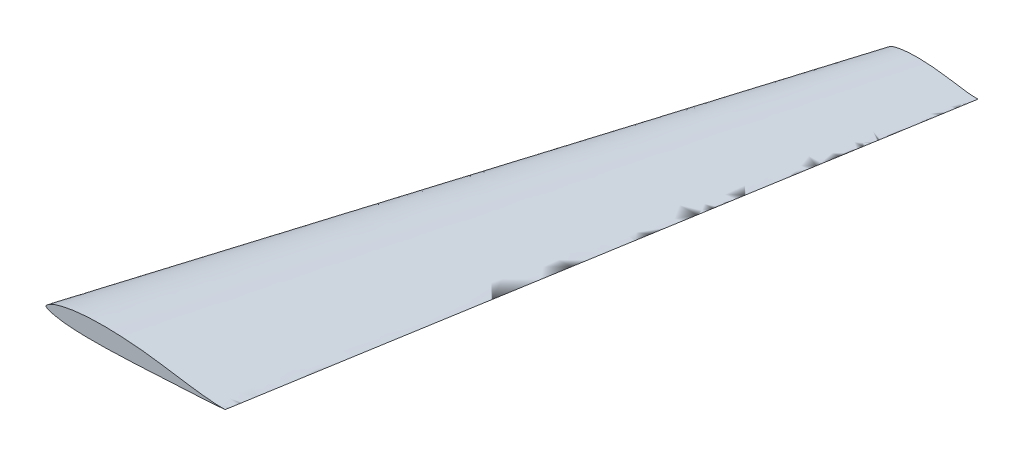
SolidWorks part; units mm, degrees
ref_plane "Front Plane" through (0, 0, 0) normal (0, 0, 1) x (1, 0, 0)
ref_plane "Top Plane" through (0, 0, 0) normal (0, 1, 0) x (1, 0, 0)
ref_plane "Right Plane" through (0, 0, 0) normal (1, 0, 0) x (0, 0, -1)
curve "Curve1"
  spline degree 3 poles (89.4117, -0.0768, 0) (90.1581, 0.0163, 0) (89.3384, -0.0489, 0) (88.6634, -0.0554, 0) (86.9988, -0.0528, 0) (84.9698, 0.0523, 0) (82.3441, 0.2429, 0) (79.2951, 0.5513, 0) (75.8494, 0.9741, 0) (72.0904, 1.4967, 0) (68.0818, 2.0963, 0) (63.8898, 2.7454, 0) (59.5721, 3.4086, 0) (55.1731, 4.0377, 0) (50.7294, 4.6, 0) (46.2733, 5.0781, 0) (41.8379, 5.4578, 0) (37.4583, 5.7341, 0) (33.171, 5.903, 0) (29.014, 5.9637, 0) (25.0243, 5.916, 0) (21.2371, 5.7575, 0) (17.6835, 5.491, 0) (14.3911, 5.12, 0) (11.385, 4.6544, 0) (8.6886, 4.1134, 0) (6.3249, 3.5134, 0) (4.3152, 2.87, 0) (2.6751, 2.2019, 0) (1.4179, 1.5316, 0) (0.6259, 0.9504, 0) (0.2409, 0.5277, 0) (0.0946, 0.3023, 0) (0.0289, 0.1579, 0) (-0.0008, 0.0428, 0) (-0.0021, -0.0493, 0) (0.0369, -0.1348, 0) (0.1141, -0.2351, 0) (0.2404, -0.3544, 0) (0.4668, -0.5223, 0) (1.0037, -0.8427, 0) (2.0204, -1.2501, 0) (3.5765, -1.7042, 0) (5.5485, -2.1302, 0) (7.9154, -2.5093, 0) (10.6594, -2.8252, 0) (13.7595, -3.0666, 0) (17.1926, -3.2314, 0) (20.9311, -3.3172, 0) (24.9437, -3.3283, 0) (29.1943, -3.2696, 0) (33.6423, -3.153, 0) (38.2418, -2.9882, 0) (42.9422, -2.7897, 0) (47.6888, -2.5669, 0) (52.4251, -2.3307, 0) (57.0933, -2.0873, 0) (61.6364, -1.844, 0) (65.999, -1.6043, 0) (70.1278, -1.373, 0) (73.9729, -1.1522, 0) (77.4858, -0.9472, 0) (80.6263, -0.7576, 0) (83.3439, -0.5873, 0) (85.6375, -0.4302, 0) (87.3906, -0.2992, 0) (88.8126, -0.1608, 0) (89.4117, -0.0768, 0) (90.1581, 0.0163, 0) (89.3384, -0.0489, 0) knots -0.013312 -0.00609 -0.00158 0 0.001669 0.006747 0.015187 0.026742 0.041155 0.058129 0.077283 0.098227 0.12058 0.143966 0.168018 0.192451 0.217075 0.24171 0.266182 0.29031 0.313903 0.336767 0.358704 0.37954 0.399122 0.417322 0.434037 0.449154 0.462553 0.474139 0.483848 0.491647 0.497539 0.499898 0.501005 0.501951 0.502492 0.502956 0.503431 0.504004 0.505035 0.506276 0.508636 0.515301 0.524213 0.535296 0.548467 0.563638 0.580726 0.599619 0.62018 0.642246 0.665633 0.690118 0.715452 0.741354 0.76752 0.793634 0.819375 0.844429 0.868488 0.891259 0.912467 0.93185 0.949165 0.964196 0.976755 0.986688 0.99391 0.99842 1 1.001669 1.006747 1.015187 periodic
sketch "CentralProfile" plane through (0, 0, 0) normal (0, 0, 1) x (1, 0, 0)
  line L0 (90, 0) -> (-10, 0) construction
  spline S1 degree 3 poles (89.3464, -0.0856) (90.1757, 0.0182) (89.2649, -0.0546) (88.5149, -0.0621) (86.6653, -0.0599) (84.4108, 0.0561) (81.4932, 0.2668) (78.1052, 0.6082) (74.2764, 1.0766) (70.0995, 1.6557) (65.6451, 2.3204) (60.9871, 3.0399) (56.1892, 3.7751) (51.3011, 4.4723) (46.3633, 5.0953) (41.4118, 5.6247) (36.4833, 6.0448) (31.6169, 6.35) (26.8531, 6.5359) (22.2341, 6.6017) (17.8011, 6.547) (13.593, 6.3694) (9.6446, 6.0718) (5.9865, 5.6583) (2.6465, 5.1398) (-0.3493, 4.5376) (-2.9754, 3.8699) (-5.2082, 3.1542) (-7.0304, 2.4112) (-8.4269, 1.6659) (-9.3068, 1.0198) (-9.7344, 0.5499) (-9.8969, 0.2994) (-9.9698, 0.1389) (-10.0028, 0.011) (-10.0042, -0.0913) (-9.9608, -0.1863) (-9.8749, -0.2977) (-9.7346, -0.4302) (-9.483, -0.6167) (-8.8862, -0.9725) (-7.7564, -1.4247) (-6.0272, -1.9287) (-3.8359, -2.4013) (-1.2058, -2.8215) (1.8433, -3.1713) (5.2881, -3.4383) (9.1027, -3.6201) (13.2568, -3.7139) (17.7152, -3.7245) (22.4382, -3.6576) (27.3805, -3.5263) (32.4911, -3.3413) (37.7137, -3.1189) (42.9878, -2.8693) (48.2503, -2.605) (53.4371, -2.3326) (58.4851, -2.0605) (63.3324, -1.7923) (67.92, -1.5337) (72.1923, -1.2867) (76.0955, -1.0576) (79.5849, -0.8456) (82.6045, -0.6553) (85.1528, -0.4797) (87.1007, -0.3335) (88.6807, -0.1791) (89.3464, -0.0856) (90.1757, 0.0182) (89.2649, -0.0546) knots -0.013312 -0.00609 -0.00158 0 0.001669 0.006747 0.015187 0.026742 0.041155 0.058129 0.077283 0.098227 0.12058 0.143966 0.168018 0.192451 0.217075 0.24171 0.266182 0.29031 0.313903 0.336767 0.358704 0.37954 0.399122 0.417322 0.434037 0.449154 0.462553 0.474139 0.483848 0.491647 0.497539 0.499898 0.501005 0.501951 0.502492 0.502956 0.503431 0.504004 0.505035 0.506276 0.508636 0.515301 0.524213 0.535296 0.548467 0.563638 0.580726 0.599619 0.62018 0.642246 0.665633 0.690118 0.715452 0.741354 0.76752 0.793634 0.819375 0.844429 0.868488 0.891259 0.912467 0.93185 0.949165 0.964196 0.976755 0.986688 0.99391 0.99842 1 1.001669 1.006747 1.015187 only from (90, 0) to (90, 0)
  point P1 (1.8051, -3.1475)
  point P2 (90, 0)
  point P4 (1.8148, 4.9626)
  dimension "D1" = 100
ref_plane "CentralProfilePlane" through (0, 0, 0) normal (0, 0, 1) x (1, 0, 0)
curve "Curve2"
  spline degree 3 poles (49.6732, -0.0427, -360) (50.0878, 0.0091, -360) (49.6325, -0.0272, -360) (49.2574, -0.0308, -360) (48.3327, -0.0294, -360) (47.2055, 0.0291, -360) (45.7467, 0.1349, -360) (44.0528, 0.3063, -360) (42.1386, 0.5412, -360) (40.0502, 0.8315, -360) (37.8232, 1.1646, -360) (35.4944, 1.5252, -360) (33.0956, 1.8937, -360) (30.6517, 2.2432, -360) (28.183, 2.5556, -360) (25.7074, 2.8212, -360) (23.2433, 3.0321, -360) (20.8102, 3.1856, -360) (18.4283, 3.2794, -360) (16.1189, 3.3132, -360) (13.9024, 3.2866, -360) (11.7984, 3.1986, -360) (9.8242, 3.0505, -360) (7.9951, 2.8444, -360) (6.325, 2.5858, -360) (4.827, 2.2852, -360) (3.5139, 1.9519, -360) (2.3974, 1.5945, -360) (1.4862, 1.2233, -360) (0.7877, 0.8509, -360) (0.3477, 0.528, -360) (0.1338, 0.2932, -360) (0.0525, 0.1679, -360) (0.0161, 0.0877, -360) (-0.0005, 0.0238, -360) (-0.0012, -0.0274, -360) (0.0205, -0.0749, -360) (0.0634, -0.1306, -360) (0.1336, -0.1969, -360) (0.2593, -0.2902, -360) (0.5576, -0.4682, -360) (1.1224, -0.6945, -360) (1.9869, -0.9468, -360) (3.0825, -1.1835, -360) (4.3974, -1.3941, -360) (5.9219, -1.5695, -360) (7.6442, -1.7037, -360) (9.5515, -1.7952, -360) (11.6284, -1.8429, -360) (13.8576, -1.849, -360) (16.2191, -1.8164, -360) (18.6902, -1.7517, -360) (21.2455, -1.6601, -360) (23.8568, -1.5499, -360) (26.4938, -1.4261, -360) (29.125, -1.2948, -360) (31.7185, -1.1596, -360) (34.2425, -1.0245, -360) (36.6661, -0.8913, -360) (38.9599, -0.7628, -360) (41.0961, -0.6401, -360) (43.0477, -0.5262, -360) (44.7924, -0.4209, -360) (46.3022, -0.3263, -360) (47.5764, -0.239, -360) (48.5503, -0.1662, -360) (49.3403, -0.0893, -360) (49.6732, -0.0427, -360) (50.0878, 0.0091, -360) (49.6325, -0.0272, -360) knots -0.013312 -0.00609 -0.00158 0 0.001669 0.006747 0.015187 0.026742 0.041155 0.058129 0.077283 0.098227 0.12058 0.143966 0.168018 0.192451 0.217075 0.24171 0.266182 0.29031 0.313903 0.336767 0.358704 0.37954 0.399122 0.417322 0.434037 0.449154 0.462553 0.474139 0.483848 0.491647 0.497539 0.499898 0.501005 0.501951 0.502492 0.502956 0.503431 0.504004 0.505035 0.506276 0.508636 0.515301 0.524213 0.535296 0.548467 0.563638 0.580726 0.599619 0.62018 0.642246 0.665633 0.690118 0.715452 0.741354 0.76752 0.793634 0.819375 0.844429 0.868488 0.891259 0.912467 0.93185 0.949165 0.964196 0.976755 0.986688 0.99391 0.99842 1 1.001669 1.006747 1.015187 periodic
ref_plane "OutsideProfilePlane" through (0, 0, -360) normal (0, 0, 1) x (1, 0, 0)
sketch "OutsideProfile" plane through (0, 0, -360) normal (0, 0, 1) x (1, 0, 0)
  line L0 (100, 0) -> (150, 0) construction
  line L1 (0, 0) -> (204.4026, 0) construction
  spline S2 degree 3 poles (149.6732, -0.0427) (150.0878, 0.0091) (149.6325, -0.0272) (149.2574, -0.0308) (148.3327, -0.0294) (147.2055, 0.0291) (145.7468, 0.1349) (144.0528, 0.3063) (142.1386, 0.5412) (140.0503, 0.8315) (137.8232, 1.1646) (135.4944, 1.5252) (133.0957, 1.8937) (130.6518, 2.2431) (128.1831, 2.5556) (125.7075, 2.8212) (123.2434, 3.0321) (120.8103, 3.1856) (118.4285, 3.2794) (116.119, 3.3132) (113.9026, 3.2866) (111.7985, 3.1986) (109.8243, 3.0505) (107.9952, 2.8444) (106.3252, 2.5858) (104.8272, 2.2852) (103.514, 1.9519) (102.3975, 1.5944) (101.4864, 1.2233) (100.7879, 0.8509) (100.3479, 0.528) (100.134, 0.2932) (100.0527, 0.1679) (100.0163, 0.0877) (99.9997, 0.0238) (99.999, -0.0274) (100.0207, -0.0749) (100.0636, -0.1306) (100.1338, -0.1969) (100.2595, -0.2902) (100.5578, -0.4682) (101.1226, -0.6945) (101.9871, -0.9468) (103.0827, -1.1835) (104.3976, -1.3941) (105.922, -1.5695) (107.6444, -1.7037) (109.5516, -1.7952) (111.6286, -1.8429) (113.8578, -1.849) (116.2192, -1.8164) (118.6903, -1.7517) (121.2456, -1.6601) (123.8569, -1.5498) (126.4939, -1.426) (129.1251, -1.2948) (131.7186, -1.1596) (134.2425, -1.0245) (136.6662, -0.8912) (138.96, -0.7628) (141.0961, -0.6401) (143.0477, -0.5262) (144.7924, -0.4209) (146.3022, -0.3263) (147.5764, -0.239) (148.5503, -0.1662) (149.3403, -0.0893) (149.6732, -0.0427) (150.0878, 0.0091) (149.6325, -0.0272) knots -0.013312 -0.00609 -0.00158 0 0.001669 0.006747 0.015187 0.026742 0.041155 0.058129 0.077283 0.098227 0.12058 0.143966 0.168018 0.192451 0.217075 0.24171 0.266182 0.29031 0.313903 0.336767 0.358704 0.37954 0.399122 0.417322 0.434037 0.449154 0.462553 0.474139 0.483848 0.491647 0.497539 0.499898 0.501005 0.501951 0.502492 0.502956 0.503431 0.504004 0.505035 0.506276 0.508636 0.515301 0.524213 0.535296 0.548467 0.563638 0.580726 0.599619 0.62018 0.642246 0.665633 0.690118 0.715452 0.741354 0.76752 0.793634 0.819375 0.844429 0.868488 0.891259 0.912467 0.93185 0.949165 0.964196 0.976755 0.986688 0.99391 0.99842 1 1.001669 1.006747 1.015187 only from (150, 0) to (150, 0)
  point P1 (100, 0)
  point P2 (90.0334, 0)
  point P6 (100, 0)
  point P7 (140, 0.1103)
  dimension "D1" = 50
  dimension "D2" = 100
ref_axis "Axis3" through (-10, 0, 0) along (0.2922, 0, -0.9564)
ref_axis "Axis7" through (94.454, 0.0098, -32.0689) along (0.1376, 0.0003, -0.9905)
loft "Loft6" add profiles "CentralProfile", "OutsideProfile" connector at (-10.0022, -0.0412, 0) connector at (100.0065, 0.0481, -360)
ref_point "Intersection CentralProfile"
mirror "Mirror1" [suppressed] about plane through (0, 0, 0) normal (0, 0, 1)
sketch "Sketch2" plane through (0, 0, 0) normal (0, 1, 0) x (1, 0, 0)
  line L0 (115, 180) -> (99.276, 180)
  line L1 (99.276, 180) -> (129.2516, 350)
  line L2 (129.2516, 350) -> (138.6111, 350)
  line L3 (138.6111, 350) -> (115, 180)
  line L4 (90, 0) -> (-0.0004, 0) construction
  line L5 (-10.4162, -1.3622) -> (173.3333, 600) construction
  line L6 (-14.4891, 0) -> (14.4891, 0) construction
  line L7 (-10, 0) -> (100, 360) construction
  line L9 (94.4982, 32.387) -> (173.3333, 600) construction
  line L10 (94.454, 32.0689) -> (144.6655, 393.5913) construction
  line L11 (173.3333, 600) -> (67.5371, 0) construction
  point P4 (0, 0)
  dimension "D1" = 180
  dimension "D2" = 170
  dimension "D3" = 80
  dimension "D4" = 26.9611
extrude "Cut-Extrude-Thin1" [suppressed] cut sketch "Sketch2" against normal blind 10 and the other way through all thin thin type one direction wall 0.2
sketch "Sketch3" [suppressed] plane through (0, 0, -180) normal (0, 0, 1) x (1, 0, 0)
  line L0 (99.276, 2.1223) -> (102.0841, -1.2243)
  line L1 (99.276, -1.3814) -> (99.276, 2.1223) construction
  spline S0 degree 3 poles (115, -0.4524) (114.8776, -0.4606) (114.7298, -0.4705) (113.8452, -0.529) (113.0619, -0.5783) (111.4535, -0.6778) (110.5522, -0.7324) (108.7215, -0.8417) (107.7163, -0.9006) (105.6893, -1.0185) (104.5915, -1.0818) (102.3928, -1.2071) (101.2159, -1.2733) (99.81, -1.3517) (99.5303, -1.3673) (99.276, -1.3814) knots 0.53561 0.53561 0.53561 0.53561 0.538022 0.538522 0.553053 0.553553 0.570368 0.570868 0.589751 0.590251 0.610959 0.611459 0.63373 0.634231 0.63926 0.63926 0.63926 0.63926 construction
  dimension "D1" = 40
sketch "Sketch5" [suppressed] plane through (0, 0, -350) normal (0, 0, -1) x (-1, 0, 0)
  line L0 (-129.2516, 2.1878) -> (-131.9779, -1.0613)
  line L1 (-129.2516, -1.207) -> (-129.2516, 2.1878) construction
  spline S0 degree 3 poles (-129.2516, -1.207) (-129.3406, -1.2023) (-129.447, -1.1967) (-130.4043, -1.1461) (-131.2899, -1.0987) (-132.9745, -1.0072) (-133.8255, -0.9605) (-135.4309, -0.8714) (-136.2372, -0.8262) (-137.5488, -0.7518) (-138.0886, -0.7208) (-138.6111, -0.6907) knots 0.595879 0.595879 0.595879 0.595879 0.598448 0.598948 0.623501 0.624002 0.64756 0.648061 0.670332 0.670832 0.685912 0.685912 0.685912 0.685912 construction
  dimension "D1" = 40
loft "Cut-Loft1" [suppressed] cut section "Sketch5" section "Sketch3"
sketch "Sketch7" plane through (0, 0, 0) normal (0, 0, 1) x (1, 0, 0)
  line L1 (-88.9568, 48.1717) -> (264.2054, 48.1717)
  line L2 (-88.9568, 48.1717) -> (-88.9568, -75.6486)
  line L3 (-88.9568, -75.6486) -> (264.2054, -75.6486)
  line L4 (264.2054, 48.1717) -> (264.2054, -75.6486)
extrude "Cut-Extrude2" [suppressed] cut sketch "Sketch7" against normal blind 0.2 from offset 100 offset against normal yes
pattern_linear "LPattern1" [suppressed] count 3 spacing 100 of bodies 136 115
sketch "Sketch11" plane through (0, 0, 0) normal (0, 1, 0) x (1, 0, 0)
  line L0 (52.5353, 164.7618) -> (52.5353, 179.7618)
  line L1 (52.5353, 179.7618) -> (48.5353, 179.7618)
  line L2 (48.5353, 179.7618) -> (48.5353, 180.7618)
  line L3 (48.5353, 180.7618) -> (52.5353, 180.7618)
  line L4 (52.5353, 180.7618) -> (52.5353, 184.7618)
  line L5 (52.5353, 184.7618) -> (62.5353, 184.7618)
  line L6 (62.5353, 184.7618) -> (62.5353, 190.7618)
  line L7 (62.5353, 190.7618) -> (72.5353, 190.7618)
  line L8 (72.5353, 190.7618) -> (72.5353, 180.7618)
  line L9 (72.5353, 180.7618) -> (76.5353, 180.7618)
  line L10 (76.5353, 180.7618) -> (76.5353, 179.7618)
  line L11 (76.5353, 179.7618) -> (72.5353, 179.7618)
  line L12 (72.5353, 179.7618) -> (72.5353, 164.7618)
  line L13 (72.5353, 164.7618) -> (52.5353, 164.7618)
  dimension "D1" = 20
  dimension "D2" = 20
  dimension "D3" = 10
  dimension "D4" = 4
  dimension "D5" = 4
  dimension "D6" = 26
  dimension "D7" = 6
  dimension "D8" = 4
  dimension "D9" = 1
  dimension "D10" = 4
extrude "Cut-Extrude3" [suppressed] cut sketch "Sketch11" against normal through all both and the other way through all
sketch "Sketch12" [suppressed] plane through (0, 0, -179.7618) normal (0, 0, -1) x (-1, 0, 0)
  line L0 (-52.5353, -2.2206) -> (-52.5353, 3.4755) construction
  line L1 (-50.7242, 0.6274) -> (-52.5353, 0.6274) construction
  line L2 (-74.7242, 1.1244) -> (-72.5353, 1.1244) construction
  line L3 (-72.5353, -2.6476) -> (-72.5353, 4.8964) construction
  circle A0 centre (-50.7242, 0.6274) radius 1
  circle A1 centre (-74.7242, 1.1244) radius 1
  dimension "D1" = 24
  dimension "D2" = 2
  dimension "D3" = 2
extrude "Cut-Extrude4" [suppressed] cut sketch "Sketch12" against normal blind 2
other "Save Bodies3" [suppressed]
ref_plane "Plane2" [suppressed] through (0, 0, -100) normal (0, 0, -1) x (-1, 0, 0)
ref_axis "Axis8" through (-10, 0, 0) along (0, 0, -1)
sketch "Sketch15" plane through (0, 0, 0) normal (0, 1, 0) x (1, 0, 0)
  line L0 (-10, 0) -> (304.7432, 232.9367) construction
  line L2 (-10, 0) -> (272.7504, 0) construction
  line L3 (-14.4891, 0) -> (14.4891, 0) construction
  line L4 (-10, 0) -> (100, 360) construction
  line L5 (72.6249, 270.4088) -> (172.6876, 135.2044) construction
  line L6 (172.6876, 135.2044) -> (272.7504, 0) construction
  point P11 (320.1315, 0)
ref_plane "Plane3" through (-3.5389, 0, -4.7818) normal (0.5949, 0, 0.8038) x (0.8038, 0, -0.5949)
sketch "Sketch16" plane through (-3.5389, 0, -4.7818) normal (0.5949, 0, 0.8038) x (0.8038, 0, -0.5949)
  line L0 (11.2151, -28.3063) -> (28.7637, 71.2171) construction
  line L3 (11.2151, 69.6877) -> (11.2151, -28.3063) construction
  dimension "D1" = 10
ref_axis "Axis9" through (5.4759, -28.3063, -11.4535) along (0.1396, 0.9848, -0.1033)
ref_point "Point1"
